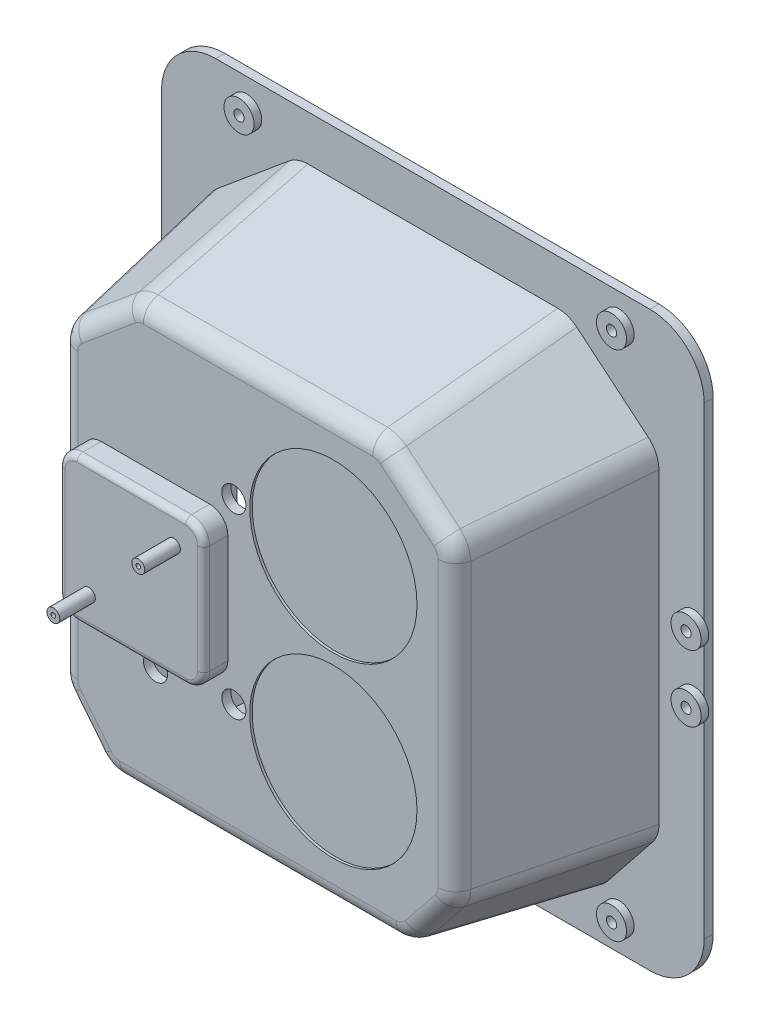
SolidWorks part; units mm, degrees
ref_plane "Front Plane" through (0, 0, 0) normal (0, 0, 1) x (1, 0, 0)
ref_plane "Top Plane" through (0, 0, 0) normal (0, 1, 0) x (1, 0, 0)
ref_plane "Right Plane" through (0, 0, 0) normal (1, 0, 0) x (0, 0, -1)
sketch "SK_Brim_180x190" plane through (0, 0, 0) normal (0, 0, 1) x (1, 0, 0)
  line L1 (-90, -95) -> (90, -95)
  line L2 (-90, -95) -> (-90, 95)
  line L3 (-90, 95) -> (90, 95)
  line L4 (90, -95) -> (90, 95)
  line L5 (-72, -77) -> (72, -77)
  line L6 (-72, -77) -> (-72, 77)
  line L7 (-72, 77) -> (72, 77)
  line L8 (72, -77) -> (72, 77)
extrude "Board_Mount_Brim_3mm" add sketch "SK_Brim_180x190" along normal blind 3
fillet "Brim_Outer_R18" radius 18 4 edges at (-90, 95, 1.5) (90, 95, 1.5) (90, -95, 1.5) (-90, -95, 1.5)
fillet "Brim_Inner_R10" radius 10 4 edges at (-72, 77, 1.5) (72, 77, 1.5) (72, -77, 1.5) (-72, -77, 1.5)
sketch "SK_Cockpit_Octagon" plane through (0, 0, 3) normal (0, 0, 1) x (1, 0, 0)
  line L0 (-55, -80) -> (55, -80)
  line L1 (55, -80) -> (75, -55)
  line L2 (75, -55) -> (75, 55)
  line L3 (75, 55) -> (45, 80)
  line L4 (45, 80) -> (-45, 80)
  line L5 (-45, 80) -> (-75, 55)
  line L6 (-75, 55) -> (-75, -55)
  line L7 (-75, -55) -> (-55, -80)
extrude "Cockpit_Canopy_Draft10deg" add sketch "SK_Cockpit_Octagon" along normal blind 58 draft 10
fillet "Canopy_Corners_R10" radius 10 8 edges at (-69.8865, -53.2063, 32) (-69.8865, 52.605, 32) (-43.1487, 74.8865, 32) (43.1487, 74.8865, 32) (69.8865, 52.605, 32) (69.8865, -53.2063, 32) (52.5423, -74.8865, 32) (-52.5423, -74.8865, 32)
fillet "Canopy_Roof_R6" radius 6 16 edges at (-57.8283, -60.0936, 61) (0, -69.773, 61) (57.8283, -60.0936, 61) (64.773, -1.1804, 61) (52.633, 60.3267, 61) (0, 69.773, 61) (-52.633, 60.3267, 61) (-64.773, -1.1804, 61) (-49.6183, -68.8027, 61) (49.6183, -68.8027, 61) (64.2184, -51.218, 61) (63.8447, 49.7752, 61) (41.0846, 69.1854, 61) (-41.0846, 69.1854, 61) (-63.8447, 49.7752, 61) (-64.2184, -51.218, 61)
sketch "SK_Symmetric_Cavity" plane through (0, 0, 0) normal (0, 0, -1) x (-1, 0, 0)
  line L0 (-53, -77) -> (53, -77)
  line L1 (57.3444, -77) -> (-57.3444, -77) construction
  line L2 (53, -77) -> (72, -52)
  line L3 (72, 57.4649) -> (72, -58.75) construction
  line L4 (72, -52) -> (72, 52)
  line L5 (72, 52) -> (43, 77)
  line L6 (-62, 77) -> (62, 77) construction
  line L7 (43, 77) -> (-43, 77)
  line L8 (-43, 77) -> (-72, 52)
  line L9 (-72, -67) -> (-72, 67) construction
  line L10 (-72, 52) -> (-72, -52)
  line L11 (-72, -52) -> (-53, -77)
extrude "Symmetric_Electronics_Cavity_58H" cut sketch "SK_Symmetric_Cavity" against normal blind 58 draft 10
sketch "Sketch7" plane through (0, 0, 61) normal (0, 0, 1) x (1, 0, 0)
  circle A0 centre (25, -29.5) radius 28.5
  circle A1 centre (25, 29.5) radius 28.5
extrude "Boss-Extrude4" add sketch "Sketch7" along normal blind 1.5
sketch "Sketch8" plane through (0, 0, 62.5) normal (0, 0, 1) x (1, 0, 0)
  circle A0 centre (25, -29.5) radius 28.5
  circle A1 centre (25, 29.5) radius 28.5
extrude "Cut-Extrude4" cut sketch "Sketch8" against normal blind 1.5
sketch "Sketch12" plane through (0, 0, 61) normal (0, 0, 1) x (1, 0, 0)
  circle A0 centre (25, -29.5) radius 27.75
extrude "Cut-Extrude8" cut sketch "Sketch12" against normal blind 0.8
sketch "Sketch13" plane through (0, 0, 61) normal (0, 0, 1) x (1, 0, 0)
  circle A0 centre (25, 29.5) radius 27.75
extrude "Cut-Extrude9" cut sketch "Sketch13" against normal blind 0.8
sketch "Sketch14" plane through (0, 0, 61) normal (0, 0, 1) x (1, 0, 0)
  line L1 (-58, -24) -> (-10, -24)
  line L2 (-58, -24) -> (-58, 24)
  line L3 (-58, 24) -> (-10, 24)
  line L4 (-10, -24) -> (-10, 24)
extrude "Boss-Extrude5" add sketch "Sketch14" along normal blind 8
fillet "Fillet3" radius 6 4 edges at (-58, 24, 65) (-10, 24, 65) (-10, -24, 65) (-58, -24, 65)
fillet "Fillet4" radius 2 8 edges at (-58, 0, 69) (-34, -24, 69) (-10, 0, 69) (-34, 24, 69) (-56.2426, -22.2426, 69) (-11.7574, -22.2426, 69) (-11.7574, 22.2426, 69) (-56.2426, 22.2426, 69)
sketch "Sketch15" plane through (0, 0, 69) normal (0, 0, 1) x (1, 0, 0)
  circle A0 centre (-48.1, -14.1) radius 2.15
  circle A1 centre (-19.9, 14.1) radius 2.15
extrude "Boss-Extrude6" add sketch "Sketch15" along normal blind 11.8
sketch "Sketch16" plane through (0, 0, 80.8) normal (0, 0, 1) x (1, 0, 0)
  circle A0 centre (-48.1, -14.1) radius 0.75
  circle A1 centre (-19.9, 14.1) radius 0.75
extrude "Cut-Extrude10" cut sketch "Sketch16" against normal blind 11.3
sketch "Sketch17" plane through (0, 0, 61) normal (0, 0, 1) x (1, 0, 0)
  circle A0 centre (-8, -29.5) radius 4
  circle A1 centre (-8, 29.5) radius 4
extrude "Cut-Extrude11" cut sketch "Sketch17" against normal blind 4
sketch "Sketch18" plane through (0, 0, 61) normal (0, 0, 1) x (1, 0, 0)
  circle A0 centre (-34, -32) radius 4
extrude "Cut-Extrude12" cut sketch "Sketch18" against normal blind 4
sketch "Sketch19" plane through (0, 0, 0) normal (0, 0, 1) x (1, 0, 0)
  line L0 (-50, -73) -> (50, -73)
  line L1 (-72, -77) -> (72, -77)
  line L2 (-72, -77) -> (-72, 77)
  line L3 (-72, 77) -> (72, 77)
  line L4 (72, -77) -> (72, 77)
  line L5 (50, -73) -> (68, -50)
  line L6 (68, -50) -> (68, 50)
  line L7 (68, 50) -> (40, 73)
  line L8 (40, 73) -> (-40, 73)
  line L9 (-40, 73) -> (-68, 50)
  line L10 (-68, 50) -> (-68, -50)
  line L11 (-68, -50) -> (-50, -73)
extrude "Boss-Extrude7" add sketch "Sketch19" along normal blind 3
sketch "Sketch20" plane through (0, 0, 3) normal (0, 0, 1) x (1, 0, 0)
  circle A0 centre (-86.5, -11) radius 1.7
  circle A1 centre (-86.5, 11) radius 1.7
  circle A2 centre (86.5, -11) radius 1.7
  circle A3 centre (86.5, 11) radius 1.7
  circle A4 centre (-61.7761, -84.9997) radius 1.7
  circle A5 centre (61.7761, -84.9997) radius 1.7
  circle A6 centre (-61.7761, 84.9997) radius 1.7
  circle A7 centre (61.7761, 84.9997) radius 1.7
extrude "Cut-Extrude13" cut sketch "Sketch20" against normal blind 3.2
sketch "Sketch21" plane through (0, 0, 3) normal (0, 0, 1) x (1, 0, 0)
  circle A0 centre (-86.5, -11) radius 5
  circle A1 centre (-86.5, -11) radius 1.7
  circle A2 centre (-86.5, 11) radius 5
  circle A3 centre (-86.5, 11) radius 1.7
  circle A4 centre (86.5, -11) radius 5
  circle A5 centre (86.5, -11) radius 1.7
  circle A6 centre (86.5, 11) radius 5
  circle A7 centre (86.5, 11) radius 1.7
  circle A8 centre (-61.7761, -84.9997) radius 5
  circle A9 centre (-61.7761, -84.9997) radius 1.7
  circle A10 centre (61.7761, -84.9997) radius 5
  circle A11 centre (61.7761, -84.9997) radius 1.7
  circle A12 centre (-61.7761, 84.9997) radius 5
  circle A13 centre (-61.7761, 84.9997) radius 1.7
  circle A14 centre (61.7761, 84.9997) radius 5
  circle A15 centre (61.7761, 84.9997) radius 1.7
extrude "Boss-Extrude8" add sketch "Sketch21" along normal blind 2.5
